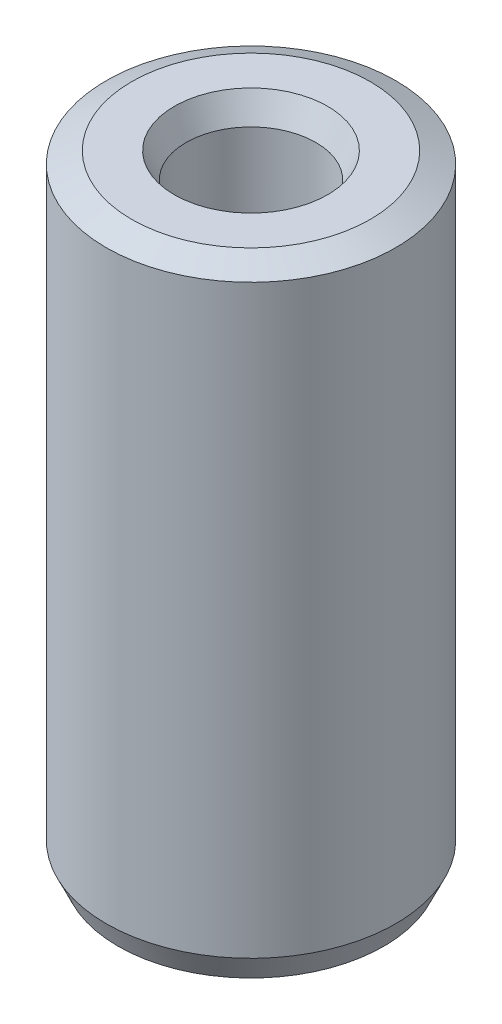
SolidWorks part; units mm, degrees
ref_plane "Front Plane" through (0, 0, 0) normal (0, 0, 1) x (1, 0, 0)
ref_plane "Top Plane" through (0, 0, 0) normal (0, 1, 0) x (1, 0, 0)
ref_plane "Right Plane" through (0, 0, 0) normal (1, 0, 0) x (0, 0, -1)
sketch "Sketch1" plane through (0, 0, 0) normal (0, 1, 0) x (1, 0, 0)
  circle A0 centre (0, 0) radius 5
  dimension "SLEEVE_OD" = 10
extrude "Boss-Extrude1" add sketch "Sketch1" along normal blind 21.511
sketch "Sketch2" plane through (0, 0, 0) normal (0, 1, 0) x (1, 0, 0)
  circle A0 centre (0, 0) radius 2.2409
  dimension "BORE_D" = 4.4817
extrude "Cut-Extrude1" cut sketch "Sketch2" along normal through all
chamfer "Chamfer1" distance 0.4076 angle 65.097 4 edges at (0, 21.511, 2.2409) (0, 0, 2.2409) (0, 0, 5) (0, 21.511, 5) first distance on face at (0, 21.511, 2.2409) first distance on face at (0, 0, 2.2409) first distance on face at (0, 21.511, 5)
